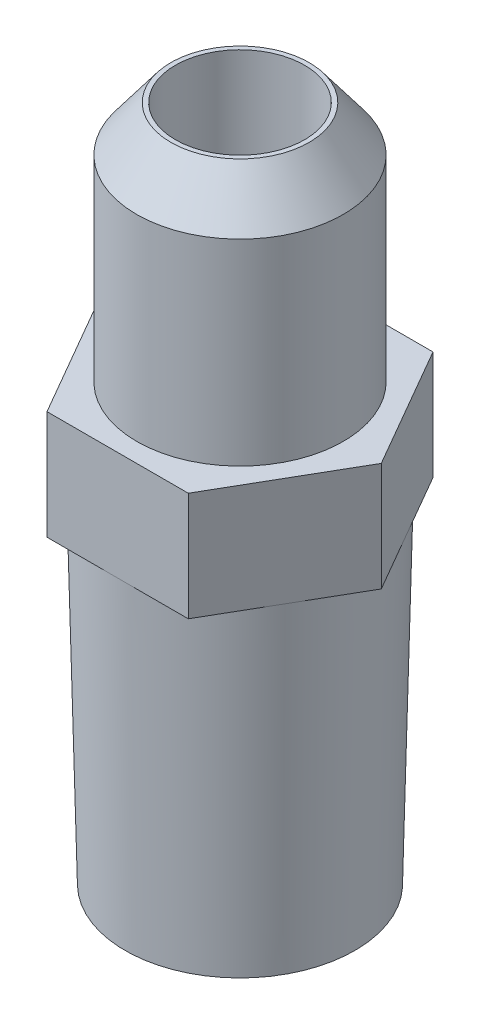
SolidWorks part; units mm, degrees
material "6061-T6 (SS)"
ref_plane "Front Plane" through (0, 0, 0) normal (0, 0, 1) x (1, 0, 0)
ref_plane "Top Plane" through (0, 0, 0) normal (0, 1, 0) x (1, 0, 0)
ref_plane "Right Plane" through (0, 0, 0) normal (1, 0, 0) x (0, 0, -1)
sketch "Sketch1" plane through (0, 0, 0) normal (0, 1, 0) x (1, 0, 0)
  line L1 (-8.2489, 0) -> (-4.1244, -7.1437)
  line L2 (-4.1244, -7.1437) -> (4.1244, -7.1438)
  line L3 (4.1244, -7.1438) -> (8.2489, 0)
  line L4 (8.2489, 0) -> (4.1244, 7.1438)
  line L5 (4.1244, 7.1438) -> (-4.1244, 7.1438)
  line L6 (-4.1244, 7.1438) -> (-8.2489, 0)
  circle A0 centre (0, 0) radius 7.1438 construction
  dimension "D1" = 14.2875
extrude "Boss-Extrude1" add sketch "Sketch1" along normal blind 6.35
sketch "Sketch2" plane through (0, 6.35, 0) normal (0, 1, 0) x (1, 0, 0)
  circle A0 centre (0, 0) radius 6.0325
  dimension "D1" = 12.065
extrude "Boss-Extrude2" add sketch "Sketch2" along normal blind 14.1224
sketch "Sketch3" plane through (0, 20.4724, 0) normal (0, 1, 0) x (1, 0, 0)
  circle A0 centre (0, 0) radius 4.0386
  circle A1 centre (0, 0) radius 16.1845
  dimension "D1" = 8.0772
extrude "Cut-Extrude1" cut sketch "Sketch3" against normal through all draft 37
sketch "Sketch6" plane through (0, 0, 0) normal (0, -1, 0) x (1, 0, 0)
  line L0 (-4.1244, -7.1438) -> (-8.2489, 0) construction
  circle A0 centre (0, 0) radius 7.1438
extrude "Boss-Extrude3" add sketch "Sketch6" along normal blind 19.05 draft 1.3
sketch "Sketch4" plane through (0, 20.4724, 0) normal (0, 1, 0) x (1, 0, 0)
  circle A0 centre (0, 0) radius 3.7719
  dimension "D1" = 7.5438
extrude "Cut-Extrude2" cut sketch "Sketch4" against normal through all
